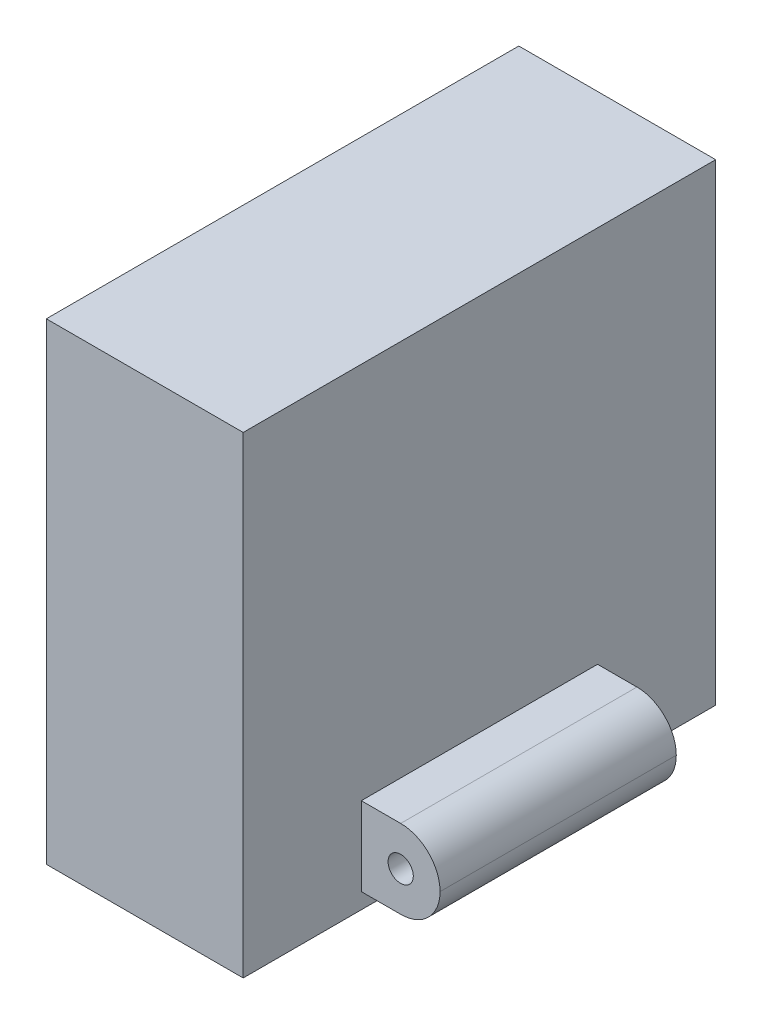
SolidWorks part; units mm, degrees
ref_plane "Front Plane" through (0, 0, 0) normal (0, 0, 1) x (1, 0, 0)
ref_plane "Top Plane" through (0, 0, 0) normal (0, 1, 0) x (1, 0, 0)
ref_plane "Right Plane" through (0, 0, 0) normal (1, 0, 0) x (0, 0, -1)
sketch "Sketch1" plane through (0, 0, 0) normal (0, 1, 0) x (1, 0, 0)
  line L1 (0, 0) -> (25, 0)
  line L2 (0, 0) -> (0, 60)
  line L3 (0, 60) -> (25, 60)
  line L4 (25, 0) -> (25, 60)
  dimension "D1" = 25
  dimension "D2" = 60
extrude "Boss-Extrude1" add sketch "Sketch1" along normal blind 60
sketch "Sketch2" plane through (25, 0, 0) normal (1, 0, 0) x (0, 0, -1)
  line L0 (30, 0) -> (30, 7)
  line L1 (0, 0) -> (60, 0) construction
  line L3 (15, 12) -> (45, 12)
  line L4 (15, 12) -> (15, 2)
  line L5 (15, 2) -> (45, 2)
  line L6 (45, 12) -> (45, 2)
  line L7 (15, 12) -> (45, 2) construction
  line L8 (15, 2) -> (45, 12) construction
  dimension "D1" = 7
  dimension "D2" = 10
  dimension "D3" = 30
extrude "Boss-Extrude2" add sketch "Sketch2" along normal blind 10 contours L4 L3 L6 L5
sketch "Sketch3" plane through (0, 0, -45) normal (0, 0, -1) x (-1, 0, 0)
  line L0 (-35, 12) -> (-25, 2)
  circle A0 centre (-30, 7) radius 1.6
  dimension "D1" = 3.2
extrude "Cut-Extrude1" cut sketch "Sketch3" against normal through all contours A0
fillet "Fillet3" radius 5 2 edges at (35, 2, -30) (35, 12, -30)
sketch "Sketch4" plane through (25, 0, 0) normal (1, 0, 0) x (0, 0, -1)
  line L0 (30, 0) -> (30, 50)
  line L1 (0, 0) -> (60, 0) construction
  dimension "D1" = 50
